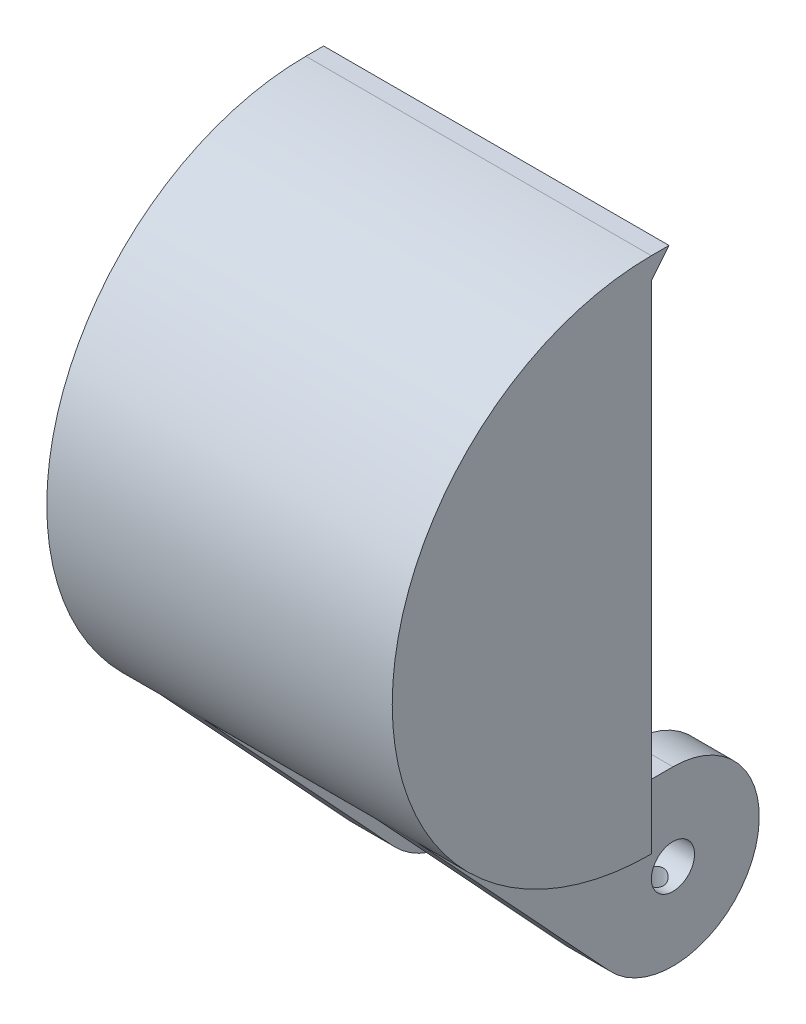
SolidWorks part; units mm, degrees
material "6061-T6 (SS)"
ref_plane "Front Plane" through (0, 0, 0) normal (0, 0, 1) x (1, 0, 0)
ref_plane "Top Plane" through (0, 0, 0) normal (0, 1, 0) x (1, 0, 0)
ref_plane "Right Plane" through (0, 0, 0) normal (1, 0, 0) x (0, 0, -1)
sketch "ExcavatorReferenceSize" plane through (0, 0, 0) normal (0, 1, 0) x (1, 0, 0)
  line L1 (-25.4, -12.7) -> (25.4, -12.7)
  line L2 (-25.4, -12.7) -> (-25.4, 12.7)
  line L3 (-25.4, 12.7) -> (25.4, 12.7)
  line L4 (25.4, -12.7) -> (25.4, 12.7)
  line L5 (-25.4, -12.7) -> (25.4, 12.7) construction
  line L6 (-25.4, 12.7) -> (25.4, -12.7) construction
  point P0 (0, 0)
  dimension "D1" = 25.4
  dimension "D2" = 50.8
sketch "Sketch2" plane through (0, 0, 0) normal (1, 0, 0) x (0, 0, -1)
  line L0 (0, 0) -> (0, 76.2)
  line L1 (0, 0) -> (8.9803, -8.9803) construction
  line L2 (0, 0) -> (0, 97.7406) construction
  arc A0 (0, 76.2) -> (0, 0) centre (0, 38.1) ccw
  dimension "D1" = 76.2
  dimension "D2" = 12.7
  dimension "D3" = 135
extrude "Boss-Extrude1" add sketch "Sketch2" along normal mid plane 50.8
shell "Shell1" thickness 3.175 removed face at (0, 38.1, 0)
chamfer "Chamfer1" [suppressed] distance 10 angle 45
sketch "Sketch4" plane through (0, 0, 0) normal (1, 0, 0) x (0, 0, -1)
  line L0 (0, 0) -> (31.6155, -31.6155) construction
  line L1 (0, 0) -> (0, 113.2937) construction
  circle A1 centre (9.525, -9.525) radius 12.7
  arc A2 (0, 73.025) -> (0, 3.175) centre (0, 38.1) ccw
  arc A3 (0, 73.025) -> (0, 3.175) centre (0, 38.1) ccw construction
  dimension "D1" = 25.4
  dimension "D2" = 135
  dimension "D3" = 12.7
extrude "Boss-Extrude3" add sketch "Sketch4" along normal mid plane 38.1
sketch "Sketch5" plane through (0, 0, 0) normal (1, 0, 0) x (0, 0, -1)
  line L1 (0, 3.175) -> (0, 0)
  line L3 (0, 0) -> (0, 76.2) construction
  line L4 (0, 3.175) -> (9.525, 3.175)
  line L5 (0, 0) -> (1.1247, 0)
  circle A0 centre (9.525, -9.525) radius 12.7 construction
  arc A1 (9.525, 3.175) -> (1.1247, 0) centre (9.525, -9.525) ccw
  dimension "D1" = 3.175
extrude "Boss-Extrude4" add sketch "Sketch5" along normal mid plane 38.1
sketch "Sketch6" plane through (0, 0, 0) normal (1, 0, 0) x (0, 0, -1)
  line L0 (0, 0) -> (12.9142, -12.9142) construction
  line L1 (0, 0) -> (0, 78.8833) construction
  circle A0 centre (9.525, -9.525) radius 12.7 construction
  circle A2 centre (9.525, -9.525) radius 12.7
  dimension "D1" = 225
extrude "Cut-Extrude2" cut sketch "Sketch6" against normal blind 12.7
extrude "Cut-Extrude3" cut sketch "Sketch6<2>" along normal blind 12.7
sketch "Sketch6<2>" plane through (0, 0, 0) normal (1, 0, 0) x (0, 0, -1) same geometry as "Sketch6"
sketch "Sketch7" plane through (-19.05, 0, 0) normal (-1, 0, 0) x (0, 0, 1)
  circle A2 centre (-9.525, -9.525) radius 12.7 construction
  circle A3 centre (-9.525, -9.525) radius 3.175
  circle A4 centre (-9.525, -9.525) radius 12.7 construction
  dimension "D1" = 6.35
extrude "Cut-Extrude4" cut sketch "Sketch7" against normal up to surface (38.1 mm away) up to face at (19.05, -4.1606, -4.835)
sketch "Sketch8" plane through (19.05, 0, 0) normal (1, 0, 0) x (0, 0, -1)
  line L3 (-27.9361, 12.1928) -> (0.213, -18.1607)
  line L6 (0.213, -18.1607) -> (5.0349, -21.4048)
  line L7 (-27.9361, 12.1928) -> (-25.2112, 13.9308)
  line L8 (5.0349, -21.4048) -> (1.1247, 0)
  line L9 (1.1247, 0) -> (0, 3.175)
  line L10 (0, 0) -> (4.7601, 0) construction
  circle A3 centre (9.525, -9.525) radius 12.7 construction
  arc A5 (0, 76.2) -> (0, 0) centre (0, 38.1) ccw construction
  arc A6 (-27.9361, 12.1928) -> (0, 0) centre (0, 38.1) ccw construction
  arc A7 (22.225, -9.525) -> (0.213, -18.1607) centre (9.525, -9.525) ccw construction
  arc A9 (0, 73.025) -> (0, 3.175) centre (0, 38.1) ccw
  arc A10 (-25.2112, 13.9308) -> (0, 3.175) centre (0, 38.1) ccw
  circle A11 centre (9.525, -9.525) radius 12.7 construction
  point P10 (1.1247, 0)
  point P11 (-27.9361, 12.1928)
  point P12 (0.213, -18.1607)
  point P18 (-25.2112, 13.9308)
extrude "Boss-Extrude5" add sketch "Sketch8" against normal up to surface (38.1 mm away) up to face at (-19.05, -9.525, -6.35)
ref_plane "Plane1" through (0, -21.4048, 0) normal (0, 1, 0) x (1, 0, 0)
sketch "Sketch9" plane through (0, 0, 0) normal (1, 0, 0) x (0, 0, -1)
  line L3 (9.525, 3.175) -> (0, 3.175)
  line L5 (0, 3.175) -> (0, 0)
  line L13 (0, 3.175) -> (0, 0)
  line L15 (-27.9361, 12.1928) -> (0.213, -18.1607)
  line L16 (-27.9361, 12.1928) -> (0.213, -18.1607)
  line L17 (9.525, 3.175) -> (0, 3.175)
  arc A2 (-27.9361, 12.1928) -> (0, 0) centre (0, 38.1) ccw
  arc A3 (0.213, -18.1607) -> (9.525, 3.175) centre (9.525, -9.525) ccw
  arc A9 (-27.9361, 12.1928) -> (0, 0) centre (0, 38.1) ccw
  arc A10 (0.213, -18.1607) -> (9.525, 3.175) centre (9.525, -9.525) ccw
  dimension "D1" = 0
extrude "Cut-Extrude5" cut sketch "Sketch9" against normal mid plane 25.4
sketch "Sketch11" plane through (0, 0, 0) normal (1, 0, 0) x (0, 0, -1)
  line L0 (0, 76.2) -> (0, 73.025)
  line L8 (9.525, -9.525) -> (1.3049, 74.6125) construction
  line L9 (0, 76.2) -> (2.6098, 76.2)
  line L10 (2.6098, 76.2) -> (0, 73.025)
  circle A2 centre (9.525, -9.525) radius 3.175 construction
  arc A4 (0, 76.2) -> (0, 0) centre (0, 38.1) ccw construction
  arc A5 (0, 76.2) -> (0, 0) centre (0, 38.1) ccw construction
  circle A6 centre (9.525, -9.525) radius 3.175 construction
  dimension "D1" = 45
extrude "Boss-Extrude6" add sketch "Sketch11" along normal mid plane 50.8 contours L10 L0 L9
ref_plane "Plane2" through (0, 73.025, 0) normal (0, -1, 0) x (-1, 0, 0)
fillet "Fillet2" radius 12.7 2 edges at (22.225, 38.1, 34.925) (-22.225, 38.1, 34.925)
sketch "Sketch12" plane through (0, -21.4048, 0) normal (0, 1, 0) x (1, 0, 0)
  line L1 (15.875, 12.7) -> (15.875, 6.35) construction
  line L2 (19.05, 0.213) -> (19.05, 22.225) construction
  line L3 (12.7, 22.225) -> (12.7, 0.213) construction
  line L4 (19.05, 0.213) -> (19.05, 22.225) construction
  line L5 (12.7, 22.225) -> (12.7, 0.213) construction
  line L6 (19.05, 11.219) -> (12.7, 11.219) construction
  line L7 (0, 0) -> (0, 34.6266) construction
  circle A0 centre (15.875, 9.525) radius 1.7526
  circle A1 centre (-15.875, 9.525) radius 1.7526
  point P4 (15.875, 9.525)
  point P13 (15.875, 11.219)
  dimension "D1" = 3.5052
extrude "Cut-Extrude6" cut sketch "Sketch12" along normal up to surface and the other way up to surface up to face at (19.05, -9.525, -12.7) other way up to face at (15.875, -11.049, -13.0168)
